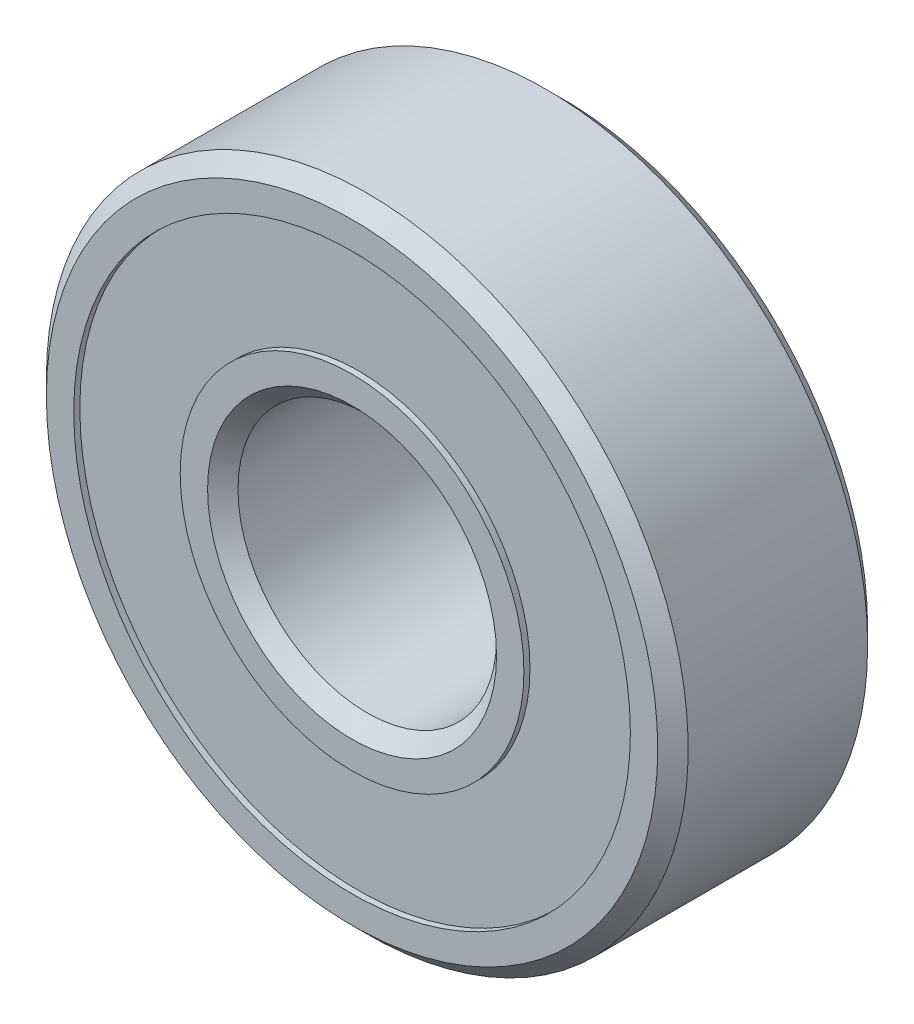
SolidWorks part; units mm, degrees
ref_plane "Plan de face" through (0, 0, 0) normal (0, 0, 1) x (1, 0, 0)
ref_plane "Plan de dessus" through (0, 0, 0) normal (0, 1, 0) x (1, 0, 0)
ref_plane "Plan de droite" through (0, 0, 0) normal (1, 0, 0) x (0, 0, -1)
sketch "Esquisse1" plane through (0, 0, 0) normal (0, 0, 1) x (1, 0, 0)
  circle A0 centre (0, 0) radius 4.25
  circle A1 centre (0, 0) radius 5.65
  circle A2 centre (0, 0) radius 9.15
  circle A3 centre (0, 0) radius 10.55
  dimension "D1" = 8.5
  dimension "D2" = 1.4
  dimension "D3" = 3.5
  dimension "D4" = 1.4
extrude "Boss.-Extru.1" add sketch "Esquisse1" along normal mid plane 6.9 contours A2 | A3
extrude "Boss.-Extru.2" add sketch "Esquisse1<3>" along normal mid plane 6.9 separate body contours A1 | A0
sketch "Esquisse1<3>" plane through (0, 0, 0) normal (0, 0, 1) x (1, 0, 0) same geometry as "Esquisse1"
extrude "Boss.-Extru.3" add sketch "Esquisse1<4>" along normal mid plane 6.5 contours A2 | A1
sketch "Esquisse1<4>" plane through (0, 0, 0) normal (0, 0, 1) x (1, 0, 0) same geometry as "Esquisse1"
chamfer "Chanfrein1" distance 0.5 angle 45 4 edges at (4.25, 0, -3.45) (10.55, 0, -3.45) (10.55, 0, 3.45) (4.25, 0, 3.45)
